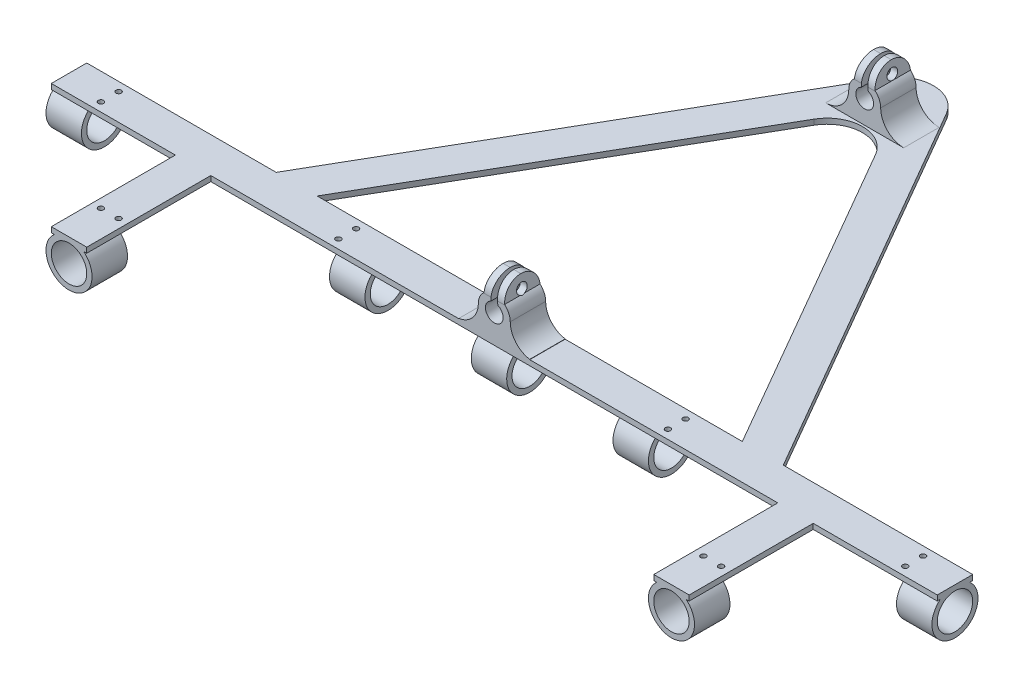
SolidWorks part; units mm, degrees
ref_plane "前视基准面" through (0, 0, 0) normal (0, 0, 1) x (1, 0, 0)
ref_plane "上视基准面" through (0, 0, 0) normal (0, 1, 0) x (1, 0, 0)
ref_plane "右视基准面" through (0, 0, 0) normal (1, 0, 0) x (0, 0, -1)
sketch "草图1" plane through (0, 0, 0) normal (0, 1, 0) x (1, 0, 0)
  line L1 (-125, 5) -> (125, 5)
  line L2 (-125, 5) -> (-125, -5)
  line L3 (-125, -5) -> (125, -5)
  line L4 (125, 5) -> (125, -5)
  line L5 (-125, 5) -> (125, -5) construction
  line L6 (-125, -5) -> (125, 5) construction
  point P0 (0, 0)
  dimension "D1" = 250
  dimension "D2" = 10
extrude "凸台-拉伸1" add sketch "草图1" along normal blind 1.5
sketch "草图4" plane through (0, 0, 0) normal (0, -1, 0) x (1, 0, 0)
  line L1 (-5, 7.1337) -> (5, 7.1337)
  line L2 (-5, 7.1337) -> (-5, -7.1337)
  line L3 (-5, -7.1337) -> (5, -7.1337)
  line L4 (5, 7.1337) -> (5, -7.1337)
  line L5 (-5, 7.1337) -> (5, -7.1337) construction
  line L6 (-5, -7.1337) -> (5, 7.1337) construction
  point P0 (0, 0)
  dimension "D1" = 10
  dimension "D2" = 14.2673
extrude "凸台-拉伸3" add sketch "草图4" along normal blind 11.5
sketch "草图5" plane through (5, 0, 0) normal (1, 0, 0) x (0, 0, -1)
  line L0 (0, 0) -> (0, -5)
  line L1 (5, 0) -> (-5, 0) construction
  line L2 (-5, 1.5) -> (5, 1.5) construction
  circle A0 centre (0, -5) radius 5
  circle A1 centre (0, -5) radius 6.5
  dimension "D1" = 10
extrude "切除-拉伸1" cut sketch "草图5" against normal through all
sketch "草图6" plane through (0, 0, 0) normal (0, -1, 0) x (1, 0, 0)
  line L0 (0, 0) -> (40, 0)
  line L1 (-125, 5) -> (125, 5) construction
  line L3 (35, 6.5) -> (45, 6.5)
  line L4 (35, 6.5) -> (35, -6.5)
  line L5 (35, -6.5) -> (45, -6.5)
  line L6 (45, 6.5) -> (45, -6.5)
  line L7 (35, 6.5) -> (45, -6.5) construction
  line L8 (35, -6.5) -> (45, 6.5) construction
  dimension "D1" = 40
  dimension "D2" = 10
  dimension "D3" = 13
extrude "凸台-拉伸4" add sketch "草图6" along normal blind 11.5 contours L3 L6 L5 L4
sketch "草图7" plane through (45, 0, 0) normal (1, 0, 0) x (0, 0, -1)
  line L0 (0, -5) -> (0, 0)
  line L1 (-5, 0) -> (5, 0) construction
  line L2 (-5, 1.5) -> (5, 1.5) construction
  circle A0 centre (0, -5) radius 5
  circle A1 centre (0, -5) radius 6.5
  dimension "D1" = 10
extrude "切除-拉伸2" cut sketch "草图7" against normal through all
sketch "草图8" plane through (0, 0, 0) normal (0, -1, 0) x (1, 0, 0)
  line L0 (0, 0) -> (120, 0)
  line L1 (-125, 5) -> (125, 5) construction
  line L3 (115, 6.5) -> (125, 6.5)
  line L4 (115, 6.5) -> (115, -6.5)
  line L5 (115, -6.5) -> (125, -6.5)
  line L6 (125, 6.5) -> (125, -6.5)
  line L7 (115, 6.5) -> (125, -6.5) construction
  line L8 (115, -6.5) -> (125, 6.5) construction
  dimension "D1" = 120
  dimension "D2" = 10
  dimension "D3" = 13
extrude "凸台-拉伸5" add sketch "草图8" along normal blind 11.5 contours L3 L6 L5 L4
sketch "草图9" plane through (125, 0, 0) normal (1, 0, 0) x (0, 0, -1)
  line L0 (0, -5) -> (0, 0)
  line L1 (-5, 1.5) -> (5, 1.5) construction
  line L2 (-5, 0) -> (5, 0)
  circle A0 centre (0, -5) radius 5
  circle A1 centre (0, -5) radius 6.5
  dimension "D1" = 10
extrude "切除-拉伸3" cut sketch "草图9" against normal through all
sketch "草图13" plane through (0, 0, 0) normal (0, -1, 0) x (1, 0, 0)
  line L0 (0, 0) -> (-40, 0)
  line L1 (-125, 5) -> (125, 5) construction
  line L3 (-45, 6.5) -> (-35, 6.5)
  line L4 (-45, 6.5) -> (-45, -6.5)
  line L5 (-45, -6.5) -> (-35, -6.5)
  line L6 (-35, 6.5) -> (-35, -6.5)
  line L7 (-45, 6.5) -> (-35, -6.5) construction
  line L8 (-45, -6.5) -> (-35, 6.5) construction
  dimension "D1" = 40
  dimension "D2" = 10
  dimension "D3" = 13
extrude "凸台-拉伸6" add sketch "草图13" along normal blind 11.5 contours L3 L6 L5 L4
sketch "草图15" plane through (-45, 0, 0) normal (-1, 0, 0) x (0, 0, 1)
  line L0 (0, 0) -> (0, -5)
  line L1 (-5, 1.5) -> (5, 1.5) construction
  circle A0 centre (0, -5) radius 5
  circle A1 centre (0, -5) radius 6.5
  dimension "D1" = 10
extrude "切除-拉伸5" cut sketch "草图15" against normal through all
sketch "草图16" plane through (0, 0, 0) normal (0, -1, 0) x (1, 0, 0)
  line L0 (0, 0) -> (-120, 0)
  line L1 (-125, 5) -> (125, 5) construction
  line L3 (-125, 6.5) -> (-115, 6.5)
  line L4 (-125, 6.5) -> (-125, -6.5)
  line L5 (-125, -6.5) -> (-115, -6.5)
  line L6 (-115, 6.5) -> (-115, -6.5)
  line L7 (-125, 6.5) -> (-115, -6.5) construction
  line L8 (-125, -6.5) -> (-115, 6.5) construction
  dimension "D1" = 120
  dimension "D2" = 10
  dimension "D3" = 13
extrude "凸台-拉伸7" add sketch "草图16" along normal blind 11.5 contours L3 L6 L5 L4
sketch "草图17" plane through (-125, 0, 0) normal (-1, 0, 0) x (0, 0, 1)
  line L0 (0, -5) -> (0, 0)
  line L1 (-5, 1.5) -> (5, 1.5) construction
  line L2 (-5, 0) -> (5, 0)
  circle A0 centre (0, -5) radius 5
  circle A1 centre (0, -5) radius 6.5
  dimension "D1" = 10
extrude "切除-拉伸6" cut sketch "草图17" against normal through all
sketch "草图18" plane through (0, 0, 0) normal (0, -1, 0) x (1, 0, 0)
  line L0 (-117.1464, 2.5) -> (-107.1464, 2.5)
  line L1 (-125, 5) -> (125, 5) construction
  line L2 (-140.924, 0) -> (135.605, 0) construction
  line L3 (0, 37.3305) -> (0, -40.1844) construction
  line L4 (-117.1464, -2.5) -> (-107.1464, -2.5)
  line L5 (117.1464, -2.5) -> (107.1464, -2.5)
  line L6 (117.1464, 2.5) -> (107.1464, 2.5)
  line L7 (-51.9294, 2.5) -> (-41.9294, 2.5)
  line L8 (-51.9294, -2.5) -> (-41.9294, -2.5)
  line L9 (51.9294, -2.5) -> (41.9294, -2.5)
  line L10 (51.9294, 2.5) -> (41.9294, 2.5)
  line L11 (-113.5, 7.6526) -> (-113.5, -7.9222)
  line L12 (-115, -6.5) -> (-115, 6.5) construction
  line L13 (-46.5, 7.6526) -> (-46.5, -7.9222)
  line L14 (-45, 6.5) -> (-45, -6.5) construction
  line L15 (46.5, 7.6526) -> (46.5, -7.9222)
  line L16 (113.5, 7.6526) -> (113.5, -7.9222)
  line L17 (-1.8696, 2.5) -> (-11.8696, 2.5)
  line L18 (-1.8696, -2.5) -> (-11.8696, -2.5)
  line L19 (-6.5, 7.6526) -> (-6.5, -7.9222)
  line L20 (-5, 6.5) -> (-5, -6.5) construction
  circle A0 centre (-113.5, 2.5) radius 0.75
  circle A1 centre (-113.5, -2.5) radius 0.75
  circle A2 centre (-46.5, 2.5) radius 0.75
  circle A3 centre (-46.5, -2.5) radius 0.75
  circle A4 centre (46.5, -2.5) radius 0.75
  circle A5 centre (46.5, 2.5) radius 0.75
  circle A6 centre (113.5, -2.5) radius 0.75
  circle A7 centre (113.5, 2.5) radius 0.75
  circle A8 centre (-6.5, 2.5) radius 0.75
  circle A9 centre (-6.5, -2.5) radius 0.75
  point P44 (-113.5, 2.5)
  point P45 (-113.5, -2.5)
  point P50 (-46.5, 2.5)
  point P51 (-46.5, -2.5)
  point P64 (-6.5, 2.5)
  point P65 (-6.5, -2.5)
  dimension "D8" = 1.5
  dimension "D9" = 1.5
  dimension "D10" = 1.5
  dimension "D1" = 2.5
  dimension "D2" = 10
  dimension "D3" = 10
  dimension "D4" = 1.5
  dimension "D5" = 1.5
  dimension "D6" = 10
  dimension "D7" = 1.5
extrude "切除-拉伸8" cut sketch "草图18" against normal through all contours L11 A0 L0 | L0 A0 L11 | L11 A0 L0 | L0 A0 L11 | A1 L4 L11 | A1 L11 L4 | A1 L4 L11 | A1 L11 L4 | L13 A2 L7 | L7 A2 L13 | L7 A2 L13 | L13 A2 L7 | A3 L8 L13 | A3 L13 L8 | A3 L13 L8 | A3 L8 L13 | L17 A8 L19 | L19 A8 L17 | L19 A8 L17 | L17 A8 L19 | A9 L18 L19 | A9 L19 L18 | A9 L18 L19 | A9 L19 L18 | A5 L10 L15 | A5 L15 L10 | A5 L10 L15 | A5 L15 L10 | L15 A4 L9 | L9 A4 L15 | L15 A4 L9 | L9 A4 L15 | A7 L6 L16 | A7 L16 L6 | A7 L6 L16 | A7 L16 L6 | L16 A6 L5 | L5 A6 L16 | L16 A6 L5 | L5 A6 L16
sketch "草图22" plane through (0, 0, 0) normal (0, -1, 0) x (1, 0, 0)
  line L0 (0, 5.038) -> (0, -222.8841) construction
  line L1 (0, 0) -> (-60, 0)
  line L2 (-125, 5) -> (125, 5) construction
  line L4 (125, -5) -> (-125, -5) construction
  line L5 (60, 0) -> (60, -5)
  line L6 (-60, -5) -> (0, -108.923)
  line L7 (0, -108.923) -> (60, -5)
  line L8 (-71.547, -5) -> (0, -128.923)
  line L9 (0, -128.923) -> (71.547, -5)
  line L10 (-60, -5) -> (-71.547, -5)
  line L11 (60, -5) -> (71.547, -5)
  line M16 (-125, -5) -> (125, -5)
  dimension "D1" = 60
  dimension "D2" = 120
  dimension "D3" = 10
extrude "凸台-拉伸10" add sketch "草图22" against normal blind 1.5 separate body contours L0 L6 L8 M16 | L7 L0 L9 M16
fillet "圆角1" radius 10 1 edges at (0, 0.75, -128.923)
fillet "圆角2" radius 10 1 edges at (0, 0.75, -108.923)
sketch "草图24" plane through (0, 1.5, 0) normal (0, 1, 0) x (1, 0, 0)
  line L1 (-10, 5) -> (10, 5)
  line L2 (-10, 5) -> (-10, -5)
  line L3 (-10, -5) -> (10, -5)
  line L4 (10, 5) -> (10, -5)
  line L5 (-10, 5) -> (10, -5) construction
  line L6 (-10, -5) -> (10, 5) construction
  point P0 (0, 0)
  dimension "D1" = 20
  dimension "D2" = 10
extrude "凸台-拉伸11" add sketch "草图24" along normal blind 20
sketch "草图25" plane through (0, 0, 5) normal (0, 0, 1) x (1, 0, 0)
  line L0 (-4.5, 8) -> (-4.5, 1.0343)
  line L1 (0, 23.6125) -> (0, -2.2867) construction
  line L2 (-125, 1.5) -> (-10, 1.5) construction
  line L3 (-11, 1.5) -> (-4.5, 1.5)
  line L4 (-1, 10.2913) -> (-0.5, 16.2913)
  line L7 (1, 10.2913) -> (0.5, 16.2913)
  line L8 (-0.5, 16.2913) -> (-2.5, 16.2913)
  line L9 (-2.5, 16.2913) -> (-2.9045, 11.4371)
  line L10 (2.5, 16.2913) -> (2.9045, 11.4371)
  line L11 (0.5, 16.2913) -> (2.5, 16.2913)
  arc A0 (-1, 10.2913) -> (1, 10.2913) centre (0, 8) ccw
  arc A1 (4.5, 8) -> (2.9045, 11.4371) centre (0, 8) ccw
  arc A2 (-11, 1.5) -> (-4.5, 8) centre (-11, 8) ccw
  arc A3 (11, 1.5) -> (4.5, 8) centre (11, 8) cw
  arc A5 (-2.9045, 11.4371) -> (-4.5, 8) centre (0, 8) ccw
  point P21 (0, 16.2913)
  line M4 (10, 1.5) -> (10, 21.5)
  line M5 (10, 21.5) -> (-10, 21.5)
  line M6 (-10, 21.5) -> (-10, 1.5)
  dimension "D1" = 5
  dimension "D3" = 9
  dimension "D6" = 0.5
  dimension "D2" = 8
  dimension "D4" = 6
  dimension "D7" = 2
extrude "切除-拉伸9" cut sketch "草图25" against normal through all contours L1 A2 A5 L9 L8 L4 A0 M5 M6 | L1 A0 L7 L11 L10 A1 A3 M5 M4
sketch "草图26" plane through (0, 1.5, 0) normal (0, 1, 0) x (1, 0, 0)
  line L0 (0, 141.3842) -> (0, -41.294) construction
  line L2 (-11, 109.5322) -> (11, 109.5322)
  line L3 (-11, 109.5322) -> (-11, 99.5322)
  line L4 (-11, 99.5322) -> (11, 99.5322)
  line L5 (11, 109.5322) -> (11, 99.5322)
  line L6 (-11, 109.5322) -> (11, 99.5322) construction
  line L7 (-11, 99.5322) -> (11, 109.5322) construction
  point P6 (0, 104.5322)
  dimension "D1" = 22
  dimension "D2" = 10
extrude "凸台-拉伸12" add sketch "草图26" along normal blind 20
sketch "草图27" plane through (0, 0, -99.5322) normal (0, 0, 1) x (1, 0, 0)
  line L0 (-4.5, 8) -> (-4.5, 0.9557)
  line L1 (-125, 1.5) -> (-10, 1.5) construction
  line L2 (-11, 1.5) -> (-4.5, 1.5)
  line L3 (0, 23.8365) -> (0, -12.7902) construction
  line L4 (-1, 10.2913) -> (-0.5, 16.2913)
  line L5 (-0.5, 16.2913) -> (-2.5, 16.2913)
  line L6 (-0.5, 16.2913) -> (-2.5, 16.2913) construction
  line L7 (-2.5, 16.2913) -> (-2.9045, 11.4371)
  line L8 (1, 10.2913) -> (0.5, 16.2913)
  line L9 (0.5, 16.2913) -> (2.5, 16.2913)
  line L10 (2.5, 16.2913) -> (2.9045, 11.4371)
  circle A0 centre (0, 8) radius 2.5
  circle A1 centre (0, 8) radius 4.5
  arc A2 (-11, 1.5) -> (-4.5, 8) centre (-11, 8) ccw
  arc A3 (11, 1.5) -> (4.5, 8) centre (11, 8) cw
  dimension "D1" = 5
  dimension "D3" = 9
  dimension "D2" = 8
extrude "切除-拉伸10" cut sketch "草图27" against normal through all contours L3 L2 A2 A1 L7 L5 L4 | L2 L3 A1 L8 L9 L10 A3 L1 | L3 A0 | A0 L3 | A1 L3 A0 L8 | L3 A1 L4 A0
fillet "圆角3" radius 5 1 edges at (1.5, 16.2913, 5)
fillet "圆角4" radius 5 1 edges at (1.5, 16.2913, -5)
fillet "圆角5" radius 5 2 edges at (-1.5, 16.2913, -5) (-1.5, 16.2913, 5)
sketch "草图28" plane through (3.831, 0.3193, 0) normal (0.9965, 0.083, 0) x (0, 0, -1)
  line L0 (0, 14.0274) -> (0, 16.0274)
  circle A0 centre (0, 12.5274) radius 1.5
  dimension "D1" = 3
  dimension "D2" = 2
extrude "切除-拉伸13" cut sketch "草图28" against normal blind 2 and the other way blind 2.3246 contours A0
sketch "草图31" plane through (-3.831, 0.3193, 0) normal (-0.9965, 0.083, 0) x (0, 0, 1)
  line L0 (0, 14.0274) -> (0, 16.0274)
  circle A0 centre (0, 12.5274) radius 1.5
  dimension "D1" = 3
  dimension "D2" = 2
extrude "切除-拉伸20" cut sketch "草图31" against normal blind 2 contours A0
sketch "草图34" plane through (-3.831, 0.3193, 0) normal (0.9965, -0.083, 0) x (0, 0, -1)
  line L0 (0, 11.1564) -> (-0.5943, 11.1564)
  line L1 (0.6086, 11.1564) -> (-0.6086, 11.1564) construction
  line L2 (0, 11.1564) -> (0.5946, 11.1564)
  circle A0 centre (0.0002, 12.5336) radius 1.5
  point P6 (-0.5942, 11.1564)
  point P8 (-0.5942, 11.1564)
  point P9 (0.5944, 11.1564)
  point P10 (-0.2282, 11.1564)
  point P11 (0.4925, 11.1564)
  line M1 (0.6086, 11.1564) -> (-0.6086, 11.1564)
  dimension "D1" = 3
extrude "切除-拉伸31" cut sketch "草图34" against normal through all contours A0 M1
fillet "圆角7" radius 5 2 edges at (-1.5, 16.2913, -109.5322) (-1.5, 16.2913, -99.5322)
sketch "草图36" plane through (-1.8448, 0.1537, 0) normal (0.9965, -0.083, 0) x (0, 0, -1)
  line L0 (104.5322, 14.1935) -> (104.5322, 16.1935)
  line L1 (109.5322, 16.4426) -> (109.5322, 11.6388) construction
  circle A0 centre (104.5322, 12.6935) radius 1.5
  ellipse E0 centre (104.5322, 11.1762) end of major axis (104.5322, 6.1588) minor radius 5 (104.5322, 16.1935) -> (99.5322, 11.1762) ccw construction
  dimension "D1" = 3
  dimension "D2" = 2
  dimension "D3" = 5
extrude "切除-拉伸32" cut sketch "草图36" against normal through all contours A0
fillet "圆角9" radius 5 2 edges at (1.5, 16.2913, -99.5322) (1.5, 16.2913, -109.5322)
sketch "草图39" plane through (1.8448, 0.1537, 0) normal (-0.9965, -0.083, 0) x (0, 0, 1)
  line L0 (-104.5322, 14.1935) -> (-104.5322, 16.1935)
  circle A0 centre (-104.5322, 12.6935) radius 1.5
  dimension "D1" = 3
  dimension "D2" = 2
extrude "切除-拉伸33" cut sketch "草图39" against normal through all contours A0
sketch "草图40" plane through (0, 1.5, 0) normal (0, -1, 0) x (1, 0, 0)
  line L0 (-8.8831, 2.5) -> (-5.3164, 2.5)
  line L1 (-6.5, 4.271) -> (-6.5, 1.1323)
  line L2 (-125, 5) -> (125, 5) construction
  line L3 (-5, 6.5) -> (-5, -6.5) construction
  line L4 (-12.5321, 0) -> (-1.8087, 0) construction
  line L5 (-2.5, 0) -> (-0.5, 0) construction
  circle A0 centre (-6.5, 2.5) radius 0.75
  circle A1 centre (-6.5, -2.5) radius 0.75
  circle M1 centre (-6.5, 2.5) radius 0.75
  dimension "D1" = 2.5
  dimension "D2" = 3.1387
  dimension "D3" = 1.5
extrude "切除-拉伸36" cut sketch "草图40" against normal through all contours L1 L0 M1 | L1 L0 M1 | L0 L1 M1 | L1 L0 M1 | A1
sketch "草图41" plane through (0, 0, 5) normal (0, 0, 1) x (1, 0, 0)
  line L0 (125, 0.75) -> (-129.8236, 0.75) construction
  line L1 (125, 1.5) -> (125, 0) construction
  line L2 (125, 0.75) -> (85, 0.75)
  line L4 (80, 1.5) -> (90, 1.5)
  line L5 (80, 1.5) -> (80, 0)
  line L6 (80, 0) -> (90, 0)
  line L7 (90, 1.5) -> (90, 0)
  line L8 (80, 1.5) -> (90, 0) construction
  line L9 (80, 0) -> (90, 1.5) construction
  dimension "D1" = 40
  dimension "D2" = 10
  dimension "D3" = 1.5
extrude "凸台-拉伸13" add sketch "草图41" along normal blind 35
sketch "草图42" plane through (0, 0, 5) normal (0, 0, 1) x (1, 0, 0)
  line L0 (-125, 0.75) -> (-85, 0.75)
  line L1 (-125, 1.5) -> (-125, 0) construction
  line L3 (-90, 1.5) -> (-80, 1.5)
  line L4 (-90, 1.5) -> (-90, 0)
  line L5 (-90, 0) -> (-80, 0)
  line L6 (-80, 1.5) -> (-80, 0)
  line L7 (-90, 1.5) -> (-80, 0) construction
  line L8 (-90, 0) -> (-80, 1.5) construction
  dimension "D1" = 40
  dimension "D2" = 10
  dimension "D3" = 1.5
extrude "凸台-拉伸14" add sketch "草图42" along normal blind 35
sketch "草图43" plane through (0, 0, 40) normal (0, 0, 1) x (1, 0, 0)
  line L0 (85, 0) -> (85, 3.5011) construction
  line L1 (80, 0) -> (90, 0) construction
  line L2 (85, -5) -> (85, 0)
  line L3 (90, 1.5) -> (80, 1.5) construction
  circle A0 centre (85, -5) radius 5
  circle A1 centre (85, -5) radius 6.5
  line M4 (80, 0) -> (90, 0)
  dimension "D1" = 10
extrude "凸台-拉伸21" add sketch "草图43" against normal blind 10 contours A1 A0 M4 | L0 A1 M4 | L0 A1 M4
sketch "草图44" plane through (0, 0, 40) normal (0, 0, 1) x (1, 0, 0)
  line L0 (-85, 0) -> (-85, 2.8539) construction
  line L1 (-90, 0) -> (-80, 0) construction
  line L2 (-85, 0) -> (-85, -4.9374) construction
  line L3 (-85, -5) -> (-85, 0)
  line L4 (-80, 1.5) -> (-90, 1.5) construction
  circle A0 centre (-85, -5) radius 5
  circle A1 centre (-85, -5) radius 6.5
  line M4 (-90, 0) -> (-80, 0)
  dimension "D1" = 10
extrude "凸台-拉伸22" add sketch "草图44" against normal blind 10 contours A1 A0 M4 | A1 M4
sketch "草图45" plane through (0, 0, 0) normal (0, -1, 0) x (1, 0, 0)
  line L0 (-87.5, 32.9839) -> (-87.5, 15.0757)
  line L1 (-90, 40) -> (-90, 5) construction
  line L2 (-85, 27.5552) -> (-85, 13.5975) construction
  line L3 (-82.5, 32.9839) -> (-82.5, 15.0757)
  line L4 (-93.2419, 28.5) -> (-76.3973, 28.5)
  line L5 (-91.5, 30) -> (-78.5, 30) construction
  line L7 (0, 29.7177) -> (0, -25.9175) construction
  circle A1 centre (-87.5, 28.5) radius 0.75
  circle A2 centre (-82.5, 28.5) radius 0.75
  circle A3 centre (82.5, 28.5) radius 0.75
  circle A4 centre (87.5, 28.5) radius 0.75
  point P12 (-87.5, 28.5)
  point P13 (-82.5, 28.5)
  dimension "D3" = 1.5
  dimension "D4" = 1.5
  dimension "D1" = 2.5
  dimension "D2" = 1.5
extrude "切除-拉伸37" cut sketch "草图45" against normal through all contours L0 A1 L4 | L4 A1 L0 | L0 A1 L4 | L4 A1 L0 | L4 A2 L3 | L3 A2 L4 | L4 A2 L3 | L3 A2 L4 | A3 | A4
